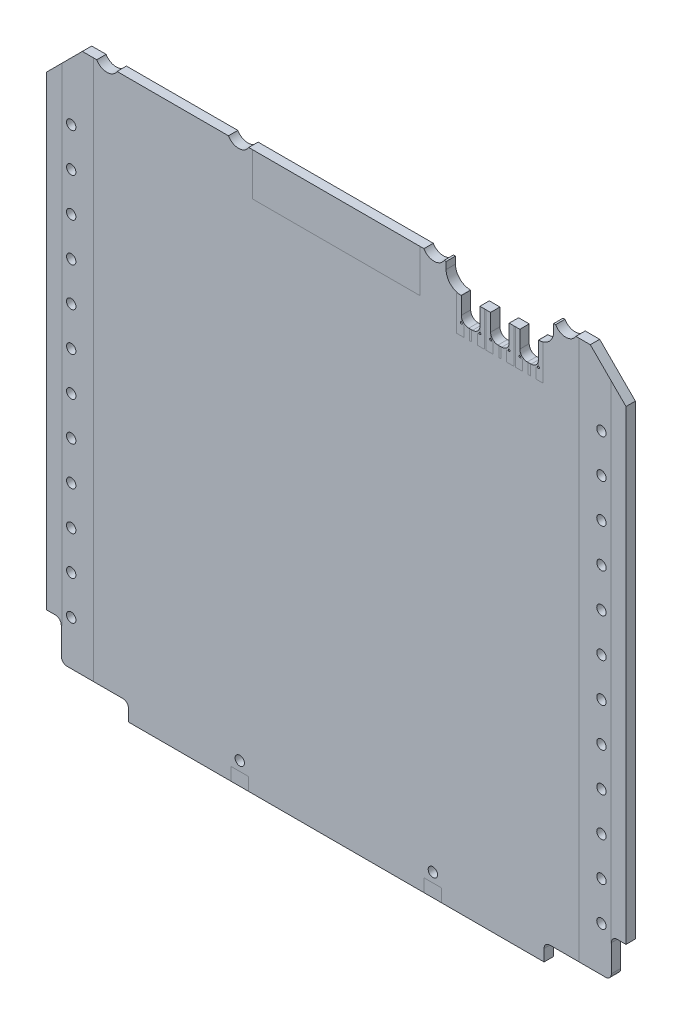
SolidWorks part; units mm, degrees
material "FR4_stuffedProtoboard"
ref_plane "Front Plane" through (0, 0, 0) normal (0, 0, 1) x (1, 0, 0)
ref_plane "Top Plane" through (0, 0, 0) normal (0, 1, 0) x (1, 0, 0)
ref_plane "Right Plane" through (0, 0, 0) normal (1, 0, 0) x (0, 0, -1)
ref_plane "Plane4" through (0, 0, -0.0125) normal (0, 0, -1) x (-1, 0, 0)
sketch "Sketch1" plane through (0, 0, -0.0125) normal (0, 0, -1) x (-1, 0, 0)
  line L4 (49.5, -50) -> (49.5, 45.3)
  line L6 (49.5, 45.3) -> (-49.5, 45.3)
  line L12 (-49.5, 45.3) -> (-49.5, -50)
  line L17 (-49.5, -50) -> (49.5, -50)
  line L18 (0, -50) -> (0, 45.3) construction
  dimension "D7" = 95.3
  dimension "D1" = 99
  dimension "D34" = 50
extrude "basicSize" add sketch "Sketch1" against normal blind 1.6
chamfer "Chamfer1" distance 6.1 angle 45 2 edges at (49.5, 45.3, 0.7875) (-49.5, 45.3, 0.7875)
sketch "Sketch4" plane through (0, 0, 1.5875) normal (0, 0, 1) x (1, 0, 0)
  line L1 (37.4679, 45.3) -> (40.9321, 45.3)
  line L7 (-43.4, 45.3) -> (43.4, 45.3) construction
  line L8 (49.5, 39.2) -> (49.5, -50) construction
  arc A0 (40.9321, 45.3) -> (37.4679, 45.3) centre (39.2, 46.3) cw
  point P5 (39.2, 44.3)
  dimension "D1" = 2
  dimension "D3" = 10.3
  dimension "D2" = 1
extrude "backplaneSideScrewCutout" cut sketch "Sketch4" against normal through all both and the other way through all
pattern_linear "LPattern3" count 2 spacing 22.5 along (-1, 0, 0) of "backplaneSideScrewCutout"
mirror "Mirror3" about plane through (0, 0, 0) normal (1, 0, 0) of "LPattern3"
sketch "Sketch6" plane through (0, 0, 1.5875) normal (0, 0, 1) x (1, 0, 0)
  line L0 (-49.5, -50) -> (-49.5, 39.2) construction
  line L1 (-49.5, -40.4) -> (-47, -40.4)
  line L2 (-49.5, -40.4) -> (-49.5, -50)
  line L4 (-47, -40.4) -> (-47, -47)
  line L5 (49.5, -50) -> (-49.5, -50) construction
  line L6 (-35.5, -50) -> (-49.5, -50)
  line L7 (-35.5, -50) -> (-35.5, -47)
  line L8 (-35.5, -47) -> (-47, -47)
  dimension "D1" = 2.5
  dimension "D2" = 3
  dimension "D3" = 9.6
  dimension "D4" = 14
extrude "Cut-Extrude4" cut sketch "Sketch6" against normal through all
fillet "Fillet1" radius 1 3 edges at (-35.5, -47, 0.7875) (-47, -47, 0.7875) (-47, -40.4, 0.7875)
mirror "Mirror1" about plane through (0, 0, 0) normal (1, 0, 0) of "Cut-Extrude4", "Fillet1"
sketch "Sketch7" plane through (0, 0, 1.5875) normal (0, 0, 1) x (1, 0, 0)
  line L0 (-14.2875, 45.5) -> (-14.2875, 39.912) construction
  line L1 (-14.2875, 45.3) -> (-14.2875, 38.007)
  line L2 (-12.2428, 38.007) -> (-11.8872, 38.007) construction
  line L3 (-14.2875, 38.007) -> (14.2875, 38.007)
  line L4 (14.2875, 45.5) -> (14.2875, 39.912) construction
  line L5 (14.2875, 45.3) -> (14.2875, 38.007)
  line L7 (-14.9679, 45.3) -> (14.9679, 45.3) construction
  line L8 (-14.2875, 45.3) -> (14.2875, 45.3)
extrude "TigerEyeFootprint" cut sketch "Sketch7" against normal blind 0.0001
sketch "thermalContacts_upper" plane through (0, 0, 1.5875) normal (0, 0, 1) x (1, 0, 0)
  line L0 (-49.5, -40.4) -> (-49.5, 39.2) construction
  line L1 (35.5, -50) -> (-35.5, -50) construction
  line L3 (-46.9, 45.3) -> (-46.9, -41.5)
  line L4 (-37.4679, 45.3) -> (-18.4321, 45.3) construction
  line L23 (-46.9, 45.3) -> (-56.3922, 45.3)
  line L24 (-56.3922, 45.3) -> (-56.3922, -41.5)
  line L25 (-56.3922, -41.5) -> (-46.9, -41.5)
  dimension "D1" = 2.6
  dimension "D2" = 8.5
extrude "keepOut_bottom" cut sketch "thermalContacts_upper" against normal blind 0.0001
sketch "Sketch3" plane through (0, 0, 1.5875) normal (0, 0, 1) x (1, 0, 0)
  line L1 (-47, -46) -> (-47, -41.5) construction
  line L2 (-36.5, -47) -> (-46, -47) construction
  line L3 (-14.9679, 45.3) -> (14.9679, 45.3) construction
  line L5 (-49.5, -40.4) -> (-49.5, 39.2) construction
  line L6 (-46.9, -41.5) -> (-46.9, 41.8) construction
  line L7 (-46.9, -41.5) -> (-47, -41.5)
  line L8 (-47, -46) -> (-47, -41.5) construction
  line L9 (-47, -41.5) -> (-46.9, -41.5) construction
  line L10 (0, -50) -> (0, 45.3) construction
  line L11 (35.5, -50) -> (-35.5, -50) construction
  line L12 (-43.4, 45.3) -> (-40.9321, 45.3) construction
  line L13 (-41.5, 45.3) -> (-46.9, 45.3)
  line L14 (-46, -47) -> (-41.5, -47)
  line L15 (-47, -41.5) -> (-47, -46)
  line L16 (-46.9, 45.3) -> (-46.9, -41.5)
  line L17 (-41.5, -47) -> (-41.5, 45.3)
  arc A3 (-47, -46) -> (-46, -47) centre (-46, -46) ccw construction
  arc A4 (-46, -47) -> (-47, -46) centre (-46, -46) cw
  dimension "D1" = 8
extrude "caution_top" cut sketch "Sketch3" against normal blind 0.0001
sketch "hold-downLocations" plane through (0, 0, 1.5875) normal (0, 0, 1) x (1, 0, 0)
  line L1 (-18, -47.8) -> (-15, -47.8) construction
  line L3 (15, -47.8) -> (18, -47.8)
  line L4 (18, -47.8) -> (18, -50)
  line L5 (35.5, -50) -> (-35.5, -50) construction
  line L6 (18, -50) -> (15, -50)
  line L7 (15, -50) -> (15, -47.8)
  line L8 (-15, -47.8) -> (-15, -50) construction
  line L9 (-15, -50) -> (-18, -50) construction
  line L10 (-18, -50) -> (-18, -47.8) construction
  line L11 (0, -50) -> (0, -47.8) construction
  line L12 (-15, -47.8) -> (15, -47.8) construction
  dimension "D1" = 3
  dimension "D2" = 2.2
  dimension "D3" = 3
  dimension "D5" = 30
extrude "hold-downFootprints" cut sketch "hold-downLocations" against normal blind 0.0001
ref_plane "midplane_Z" through (0, 0, 0.7875) normal (0, 0, 1) x (1, 0, 0)
mirror "clearances_top-bottom" about plane through (0, 0, 0.7875) normal (0, 0, 1) of "hold-downFootprints", "caution_top", "keepOut_bottom"
mirror "clearances_side-side" about plane through (0, 0, 0) normal (1, 0, 0) of "clearances_top-bottom"
sketch "Sketch10" plane through (0, 0, -0.0125) normal (0, 0, -1) x (-1, 0, 0)
  line L0 (-15, -47.8) -> (-15, -50) construction
  line L1 (-18, -47.8) -> (-15, -47.8)
  line L2 (-18, -47.8) -> (-18, -44.5)
  line L3 (-18, -44.5) -> (-15, -44.5)
  line L4 (-15, -47.8) -> (-15, -44.5)
  line L5 (-15, -50) -> (15, -50) construction
  line L6 (0, -50) -> (0, -41.5199) construction
  line L7 (15, -47.8) -> (15, -44.5)
  line L8 (18, -44.5) -> (15, -44.5)
  line L9 (18, -47.8) -> (18, -44.5)
  line L10 (18, -47.8) -> (15, -47.8)
  dimension "D1" = 5.5
extrude "bottomsideShelfKeepouts" cut sketch "Sketch10" against normal up to surface (0.0001 mm away) up to face at (16.5, -48.9, -0.0124)
sketch "recommendedBuildArea" [suppressed] plane through (0, 0, 1.5875) normal (0, 0, 1) x (1, 0, 0)
  line L0 (51.1146, 38.007) -> (51.1146, 56.8216) construction
  line L1 (-35.5, -45.5) -> (-46.8, -45.5) construction
  line L2 (-35.5, -47) -> (-35.5, -45.5) construction
  line L3 (35.5, -47) -> (35.5, -45.5) construction
  line L4 (14.2875, 45.3) -> (-14.2875, 45.3)
  line L5 (-14.2875, 45.3) -> (-14.2875, 38.007)
  line L6 (-14.2875, 38.007) -> (14.2875, 38.007)
  line L7 (-46.8, 41.9) -> (-49.5, 39.2)
  line L8 (-49.5, 39.2) -> (-49.5, -40.4)
  line L9 (-49.5, -40.4) -> (-48, -40.4)
  line L10 (-46.8, -41.5) -> (-46.8, 41.9)
  line L11 (-47, -41.4) -> (-47, -41.5)
  line L12 (-47, -41.4) -> (-47, -41.5)
  line L13 (-47, -41.5) -> (-46.8, -41.5)
  line L14 (35.5, -45.5) -> (46.8, -45.5) construction
  line L15 (54.1146, 35.007) -> (54.1146, 77.997)
  line L16 (54.1146, 77.997) -> (43.8, 42.325)
  line L17 (-46.8, -45.5) -> (-46.8, 41.9) construction
  line L20 (43.8, 42.325) -> (43.8, -42.5)
  line L21 (14.2875, 38.007) -> (14.2875, 45.3)
  line L22 (32.5, -42.5) -> (43.8, -42.5)
  line L23 (-14.2875, 45.3) -> (-14.2875, 38.007)
  line L24 (-14.2875, 38.007) -> (51.1146, 38.007)
  line L25 (32.5, -47) -> (32.5, -42.5)
  line L26 (32.5, -47) -> (32.5, -47)
  line L27 (21, -47) -> (32.5, -47)
  line L28 (21, -45) -> (21, -47)
  line L29 (46.8, -41.5) -> (47, -41.5)
  line L30 (46.8, -41.5) -> (47, -41.5)
  line L31 (46.8, 41.9) -> (46.8, -41.5)
  line L32 (48, -40.4) -> (49.5, -40.4)
  line L33 (49.5, -40.4) -> (49.5, 39.2)
  line L34 (49.5, 39.2) -> (46.8, 41.9)
  line L35 (47, -41.5) -> (47, -41.4)
  line L36 (12, -45) -> (21, -45)
  line L37 (47, -41.5) -> (47, -41.4)
  line L38 (46.8, 41.9) -> (46.8, -45.5) construction
  line L39 (12, -47) -> (12, -45)
  line L40 (-12, -47) -> (12, -47)
  line L41 (-12, -45) -> (-12, -47)
  line L42 (-21, -45) -> (-12, -45)
  line L43 (-21, -47) -> (-21, -45)
  line L44 (-32.5, -47) -> (-21, -47)
  line L45 (-32.5, -47) -> (-32.5, -47)
  line L46 (-32.5, -47) -> (-32.5, -42.5)
  line L47 (-32.5, -42.5) -> (-43.8, -42.5)
  line L48 (-43.8, -42.5) -> (-43.8, 34.7661)
  line L49 (-43.8, 34.7661) -> (-43.8, 34.7661)
  line L50 (-43.8, 34.7661) -> (-39.8793, 42.3)
  line L51 (-17.2875, 42.3) -> (-39.8793, 42.3)
  line L52 (-17.2875, 42.3) -> (-17.2875, 35.007)
  line L53 (-17.2875, 35.007) -> (54.1146, 35.007)
  line L59 (-47, -41.5) -> (-46.8, -41.5)
  line L72 (-15, -48) -> (-15, -50)
  line L73 (-15, -50) -> (15, -50)
  line L74 (15, -50) -> (15, -48)
  line L75 (15, -48) -> (18, -48)
  line L76 (18, -48) -> (18, -50)
  line L77 (18, -50) -> (35.5, -50)
  line L78 (35.5, -50) -> (35.5, -48)
  line L79 (36.5, -47) -> (41.5, -47)
  line L80 (41.5, -47) -> (41.5, 45.3)
  line L81 (41.5, 45.3) -> (40.9321, 45.3)
  line L82 (37.4679, 45.3) -> (34.25, 45.3)
  line L83 (34.25, 45.3) -> (34.25, 38.35)
  line L84 (34.25, 38.35) -> (30.75, 38.35)
  line L85 (30.75, 38.35) -> (30.75, 45.3)
  line L86 (30.75, 45.3) -> (29.25, 45.3)
  line L87 (29.25, 45.3) -> (29.25, 38.35)
  line L88 (29.25, 38.35) -> (25.75, 38.35)
  line L89 (25.75, 38.35) -> (25.75, 45.3)
  line L90 (25.75, 45.3) -> (24.25, 45.3)
  line L91 (24.25, 45.3) -> (24.25, 38.35)
  line L92 (24.25, 38.35) -> (20.75, 38.35)
  line L93 (20.75, 38.35) -> (20.75, 45.3)
  line L94 (20.75, 45.3) -> (18.4321, 45.3)
  line L95 (14.9679, 45.3) -> (14.2875, 45.3)
  line L96 (14.2875, 45.3) -> (14.2875, 38.007)
  line L97 (14.2875, 38.007) -> (-14.2875, 38.007)
  line L98 (-14.2875, 38.007) -> (-14.2875, 45.3)
  line L99 (-14.2875, 45.3) -> (-14.9679, 45.3)
  line L100 (-18.4321, 45.3) -> (-37.4679, 45.3)
  line L101 (-40.9321, 45.3) -> (-41.5, 45.3)
  line L102 (41.5, -47) -> (41.5, 45.3)
  line L103 (-41.5, -47) -> (-36.5, -47)
  line L104 (-35.5, -48) -> (-35.5, -50)
  line L105 (-35.5, -50) -> (-18, -50)
  line L106 (-18, -50) -> (-18, -48)
  line L107 (-18, -48) -> (-15, -48)
  line L108 (-15, -48) -> (-15, -50) construction
  line L109 (-15, -50) -> (15, -50) construction
  line L110 (15, -50) -> (15, -48) construction
  line L111 (15, -48) -> (18, -48) construction
  line L112 (18, -48) -> (18, -50) construction
  line L113 (18, -50) -> (35.5, -50) construction
  line L114 (35.5, -50) -> (35.5, -47) construction
  line L115 (35.5, -47) -> (41.5, -47) construction
  line L133 (51.1146, 38.007) -> (-14.2875, 38.007)
  line L134 (-14.2875, 38.007) -> (-14.2875, 45.3)
  line L136 (-14.2875, 45.3) -> (-41.7, 45.3) construction
  line L139 (-41.5, -47) -> (-35.5, -47) construction
  line L140 (-35.5, -47) -> (-35.5, -50) construction
  line L141 (-35.5, -50) -> (-18, -50) construction
  line L142 (-18, -50) -> (-18, -48) construction
  line L143 (-18, -48) -> (-15, -48) construction
  line L144 (-46.8, 35.5) -> (-41.7, 45.3) construction
  line L160 (-41.5, 45.3) -> (-41.5, -47)
  line L161 (-41.5, 45.3) -> (-41.5, -47)
  line L162 (-46.8, 41.9) -> (-46.8, 35.5) construction
  line L163 (51.1146, 56.8216) -> (46.8, 41.9) construction
  arc A1 (-47, -41.4) -> (-48, -40.4) centre (-48, -41.4) ccw
  arc A3 (48, -40.4) -> (47, -41.4) centre (48, -41.4) ccw
  arc A10 (36.5, -47) -> (35.5, -48) centre (36.5, -48) ccw
  arc A11 (37.4679, 45.3) -> (40.9321, 45.3) centre (39.2, 46.3) ccw
  arc A12 (14.9679, 45.3) -> (18.4321, 45.3) centre (16.7, 46.3) ccw
  arc A13 (-18.4321, 45.3) -> (-14.9679, 45.3) centre (-16.7, 46.3) ccw
  arc A14 (-40.9321, 45.3) -> (-37.4679, 45.3) centre (-39.2, 46.3) ccw
  arc A15 (-35.5, -48) -> (-36.5, -47) centre (-36.5, -48) ccw
  dimension "D5" = 1.5
  dimension "D1" = 0
  dimension "D2" = 0
  dimension "D3" = 0
  dimension "D4" = 0
  dimension "D6" = 3
ref_point "rail midpoint"
sketch "locatorSketch" plane through (0, 0, 1.5875) normal (0, 0, 1) x (1, 0, 0)
  line L0 (-12.2428, 39.531) -> (12.2428, 38.007) construction
  line L1 (12.2428, 39.531) -> (-12.2428, 38.007) construction
  line L2 (-21.9628, 39.277) -> (-33.0372, 38.261) construction
  line L3 (-33.0372, 39.277) -> (-21.9628, 38.261) construction
  line L4 (-12.2428, 38.261) -> (-12.2428, 38.007)
  line L5 (-11.8872, 38.261) -> (-12.2428, 38.261)
  line L6 (-11.8872, 38.007) -> (-11.8872, 38.261)
  line L7 (-12.2428, 38.007) -> (-11.8872, 38.007)
  line L8 (-12.2428, 38.261) -> (-12.2428, 38.007)
  line L9 (-11.8872, 38.261) -> (-12.2428, 38.261)
  line L10 (-11.8872, 38.007) -> (-11.8872, 38.261)
  line L11 (-12.2428, 38.007) -> (-11.8872, 38.007)
  line L12 (-12.2428, 39.531) -> (-12.2428, 39.277)
  line L13 (-11.8872, 39.531) -> (-12.2428, 39.531)
  line L14 (-11.8872, 39.277) -> (-11.8872, 39.531)
  line L15 (-12.2428, 39.277) -> (-11.8872, 39.277)
  line L16 (-12.2428, 39.531) -> (-12.2428, 39.277)
  line L17 (-11.8872, 39.531) -> (-12.2428, 39.531)
  line L18 (-11.8872, 39.277) -> (-11.8872, 39.531)
  line L19 (-12.2428, 39.277) -> (-11.8872, 39.277)
  line L20 (11.8872, 39.531) -> (11.8872, 39.277)
  line L21 (12.2428, 39.531) -> (11.8872, 39.531)
  line L22 (12.2428, 39.277) -> (12.2428, 39.531)
  line L23 (11.8872, 39.277) -> (12.2428, 39.277)
  line L24 (11.8872, 39.531) -> (11.8872, 39.277)
  line L25 (12.2428, 39.531) -> (11.8872, 39.531)
  line L26 (12.2428, 39.277) -> (12.2428, 39.531)
  line L27 (11.8872, 39.277) -> (12.2428, 39.277)
  line L28 (11.8872, 38.261) -> (11.8872, 38.007)
  line L29 (12.2428, 38.261) -> (11.8872, 38.261)
  line L30 (12.2428, 38.007) -> (12.2428, 38.261)
  line L31 (11.8872, 38.007) -> (12.2428, 38.007)
  line L32 (11.8872, 38.261) -> (11.8872, 38.007)
  line L33 (12.2428, 38.261) -> (11.8872, 38.261)
  line L34 (12.2428, 38.007) -> (12.2428, 38.261)
  line L35 (11.8872, 38.007) -> (12.2428, 38.007)
  line L38 (-21.9628, 39.531) -> (-21.9628, 39.277)
  line L39 (-21.6072, 39.531) -> (-21.9628, 39.531)
  line L40 (-21.6072, 39.277) -> (-21.6072, 39.531)
  line L41 (-21.9628, 39.277) -> (-21.6072, 39.277)
  line L42 (-21.9628, 39.531) -> (-21.9628, 39.277)
  line L43 (-21.6072, 39.531) -> (-21.9628, 39.531)
  line L44 (-21.6072, 39.277) -> (-21.6072, 39.531)
  line L45 (-21.9628, 39.277) -> (-21.6072, 39.277)
  line L46 (-33.3928, 38.261) -> (-33.3928, 38.007)
  line L47 (-33.0372, 38.261) -> (-33.3928, 38.261)
  line L48 (-33.0372, 38.007) -> (-33.0372, 38.261)
  line L49 (-33.3928, 38.007) -> (-33.0372, 38.007)
  line L50 (-33.3928, 38.261) -> (-33.3928, 38.007)
  line L51 (-33.0372, 38.261) -> (-33.3928, 38.261)
  line L52 (-33.0372, 38.007) -> (-33.0372, 38.261)
  line L53 (-33.3928, 38.007) -> (-33.0372, 38.007)
  line L55 (-21.9628, 38.261) -> (-21.9628, 38.007)
  line L56 (-21.6072, 38.261) -> (-21.9628, 38.261)
  line L57 (-21.6072, 38.007) -> (-21.6072, 38.261)
  line L58 (-21.9628, 38.007) -> (-21.6072, 38.007)
  line L59 (-21.9628, 38.261) -> (-21.9628, 38.007)
  line L60 (-21.6072, 38.261) -> (-21.9628, 38.261)
  line L61 (-21.6072, 38.007) -> (-21.6072, 38.261)
  line L62 (-21.9628, 38.007) -> (-21.6072, 38.007)
  line L63 (-33.3928, 39.531) -> (-33.3928, 39.277)
  line L64 (-33.0372, 39.531) -> (-33.3928, 39.531)
  line L65 (-33.0372, 39.277) -> (-33.0372, 39.531)
  line L66 (-33.3928, 39.277) -> (-33.0372, 39.277)
  line L67 (-33.3928, 39.531) -> (-33.3928, 39.277)
  line L68 (-33.0372, 39.531) -> (-33.3928, 39.531)
  line L69 (-33.0372, 39.277) -> (-33.0372, 39.531)
  line L70 (-33.3928, 39.277) -> (-33.0372, 39.277)
  dimension "D1" = 0
  dimension "D2" = 0
  dimension "D3" = 0
  dimension "D4" = 0
  dimension "D5" = 0
  dimension "D6" = 0
  dimension "D7" = 0
  dimension "D8" = 0
sketch "Sketch8" plane through (0, 0, 1.5875) normal (0, 0, 1) x (1, 0, 0)
  line L0 (-49.5, -40.4) -> (-48, -40.4) construction
  line L2 (-49.5, -40.4) -> (-49.5, 39.2) construction
  line L3 (-41.5, 45.3) -> (-43.4, 45.3) construction
  line L4 (-18, -47.8) -> (-15, -47.8) construction
  line L5 (-45.3, 33.5) -> (-46.9, 33.5) construction
  line L6 (-46.9, 41.8) -> (-46.9, -41.5) construction
  line L7 (-16.5, -46.2) -> (-16.5, -47.8) construction
  line L8 (-18, -47.8) -> (-15, -47.8) construction
  circle A0 centre (-45.3, 33.5) radius 0.8
  circle A1 centre (-45.3, 26.8727) radius 0.8
  circle A2 centre (-45.3, 20.2455) radius 0.8
  circle A3 centre (-45.3, 13.6182) radius 0.8
  circle A4 centre (-45.3, 6.9909) radius 0.8
  circle A5 centre (-45.3, 0.3636) radius 0.8
  circle A6 centre (-45.3, -6.2636) radius 0.8
  circle A7 centre (-45.3, -12.8909) radius 0.8
  circle A8 centre (-45.3, -19.5182) radius 0.8
  circle A9 centre (-45.3, -26.1455) radius 0.8
  circle A10 centre (-45.3, -32.7727) radius 0.8
  circle A11 centre (-45.3, -39.4) radius 0.8
  circle A12 centre (-16.5, -46.2) radius 0.8
  point P35 (-16.5, -47.8)
  dimension "D1" = 1.6
  dimension "D3" = 1
  dimension "D5" = 4.2
  dimension "D6" = 11.8
  dimension "D2" = 12
extrude "springPinHoleSeed" cut sketch "Sketch8" against normal blind 10
mirror "Mirror4" about plane through (0, 0, 0) normal (1, 0, 0) of "springPinHoleSeed"
sketch "Sketch9" plane through (0, 0, 1.5875) normal (0, 0, 1) x (1, 0, 0)
  circle A0 centre (-45.3, 33.5) radius 1.35
  dimension "D1" = 2.7
sketch "bottomsideKeepout_trace" plane through (0, 0, -0.0125) normal (0, 0, -1) x (-1, 0, 0)
  line L0 (18, -50) -> (18, -44.5) construction
  line L1 (18, -44.5) -> (15, -44.5) construction
  line L2 (15, -44.5) -> (15, -50) construction
  line L3 (-15, -44.5) -> (-15, -50) construction
  line L4 (-15, -44.5) -> (-18, -44.5) construction
  line L5 (-18, -50) -> (-18, -44.5) construction
  line L6 (18, -50) -> (18, -44.5)
  line L7 (18, -44.5) -> (15, -44.5)
  line L8 (15, -44.5) -> (15, -50)
  line L9 (-15, -44.5) -> (-15, -50)
  line L10 (-15, -44.5) -> (-18, -44.5)
  line L11 (-18, -50) -> (-18, -44.5)
  line L12 (15, -50) -> (18, -50) construction
  line L13 (-15, -50) -> (-18, -50) construction
  line L14 (15, -50) -> (18, -50)
  line L15 (-15, -50) -> (-18, -50)
sketch "Sketch11" plane through (0, 0, 1.5875) normal (0, 0, 1) x (1, 0, 0)
  line L6 (34.54, 41.56) -> (31.36, 41.56)
  line L8 (34.54, 41.56) -> (34.54, 37.36)
  line L11 (34.54, 37.36) -> (31.36, 37.36)
  line L12 (31.36, 41.56) -> (31.36, 37.36)
  line L13 (34.54, 41.56) -> (31.36, 37.36) construction
  line L14 (34.54, 37.36) -> (31.36, 41.56) construction
  line L18 (29.54, 41.56) -> (26.36, 41.56)
  line L19 (29.54, 41.56) -> (29.54, 37.36)
  line L20 (29.54, 37.36) -> (26.36, 37.36)
  line L21 (26.36, 41.56) -> (26.36, 37.36)
  line L22 (29.54, 41.56) -> (26.36, 37.36) construction
  line L23 (29.54, 37.36) -> (26.36, 41.56) construction
  line L24 (24.54, 41.56) -> (21.36, 41.56)
  line L25 (24.54, 41.56) -> (24.54, 37.36)
  line L26 (24.54, 37.36) -> (21.36, 37.36)
  line L27 (21.36, 41.56) -> (21.36, 37.36)
  line L28 (24.54, 41.56) -> (21.36, 37.36) construction
  line L29 (24.54, 37.36) -> (21.36, 41.56) construction
  line L30 (18.4321, 45.3) -> (37.4679, 45.3) construction
  line L31 (16.7, 46.3) -> (39.2, 46.3) construction
  point P4 (32.95, 39.46)
  point P10 (27.95, 46.3)
  point P15 (27.95, 39.46)
  point P20 (22.95, 39.46)
  dimension "D5" = 5
  dimension "D1" = 3.18
  dimension "D2" = 4.2
  dimension "D4" = 3
  dimension "D6" = 3.74
extrude "Cut-Extrude5" cut sketch "Sketch11" against normal blind 10
fillet "Fillet2" radius 1.27 6 edges at (24.54, 37.36, 0.7875) (29.54, 37.36, 0.7875) (34.54, 37.36, 0.7875) (31.36, 37.36, 0.7875) (26.36, 37.36, 0.7875) (21.36, 37.36, 0.7875)
hole_wizard "Ø0.32 (0.32) Diameter Hole1" positions "Sketch12" profile "Sketch13" hole size "Ø0.32" standard "ANSI Metric"
sketch "Sketch12" plane through (0, 0, 1.5875) normal (0, 0, 1) x (1, 0, 0)
  line L1 (34.54, 38.63) -> (34.54, 41.56) construction
  line L2 (31.36, 41.56) -> (31.36, 38.63) construction
  line L3 (32.95, 37.36) -> (34.7997, 37.36) construction
  line L4 (32.63, 37.36) -> (33.27, 37.36) construction
  point P0 (34.54, 37.52)
  point P2 (31.36, 37.52)
  point P16 (29.54, 37.52)
  point P17 (26.36, 37.52)
  point P18 (24.54, 37.52)
  point P19 (21.36, 37.52)
  dimension "D2" = 5
  dimension "D3" = 0.16
  dimension "D1" = 3
sketch "Sketch13" plane through (34.54, 37.52, 1.5875) normal (1, 0, 0) x (0, -1, 0)
  line L0 (0, 0) -> (0, 9.6211)
  line L1 (0, 9.6211) -> (0.16, 9.525)
  line L2 (0.16, 9.525) -> (0.16, 0)
  line L5 (0.16, 0) -> (0, 0)
  line L10 (0, 9.6211) -> (-0.16, 9.525) construction
  line L11 (0, -6.35) -> (0, 107.95) construction
  dimension "Hole Dia." = 0.32
  dimension "Hole Depth" = 9.525
  dimension "Drill Angle" = 118
sketch "Sketch14" plane through (0, 0, 1.5875) normal (0, 0, 1) x (1, 0, 0)
  line L1 (35.325, 41.56) -> (34.54, 41.56)
  line L2 (35.325, 41.56) -> (35.325, 35.57)
  line L3 (35.325, 35.57) -> (34.095, 35.57)
  line L4 (30.575, 41.56) -> (30.575, 35.57)
  line L5 (35.325, 41.56) -> (30.575, 35.57) construction
  line L6 (35.325, 35.57) -> (30.575, 41.56) construction
  line L7 (32.95, 37.36) -> (32.95, 35.57) construction
  line L8 (32.63, 37.36) -> (33.27, 37.36) construction
  line L9 (31.805, 35.57) -> (31.805, 37.36)
  line L10 (32.76, 37.36) -> (33.14, 37.36)
  line L11 (32.76, 37.36) -> (32.76, 35.57)
  line L12 (32.76, 35.57) -> (33.14, 35.57)
  line L13 (33.14, 37.36) -> (33.14, 35.57)
  line L14 (32.76, 37.36) -> (33.14, 35.57) construction
  line L15 (32.76, 35.57) -> (33.14, 37.36) construction
  line L16 (34.095, 35.57) -> (34.095, 37.36)
  line L17 (33.14, 35.57) -> (32.76, 35.57)
  line L18 (31.36, 41.56) -> (31.36, 38.63) construction
  line L19 (34.54, 38.63) -> (34.54, 41.56) construction
  line L20 (31.36, 41.56) -> (31.36, 38.63)
  line L21 (34.54, 38.63) -> (34.54, 41.56)
  line L22 (32.76, 37.36) -> (33.14, 37.36)
  line L23 (31.36, 41.56) -> (30.575, 41.56)
  line L24 (31.805, 37.36) -> (31.36, 37.36)
  line L25 (34.095, 37.36) -> (34.54, 37.36)
  line L26 (31.36, 37.68) -> (31.36, 38.63)
  line L27 (34.54, 37.68) -> (34.54, 38.63)
  line L28 (31.805, 35.57) -> (30.575, 35.57)
  circle A2 centre (31.36, 37.52) radius 0.16 construction
  circle A3 centre (34.54, 37.52) radius 0.16 construction
  arc A6 (31.36, 37.68) -> (31.36, 37.36) centre (31.36, 37.52) ccw
  arc A7 (34.54, 37.36) -> (34.54, 37.68) centre (34.54, 37.52) ccw
  point P4 (32.95, 38.565)
  point P15 (32.95, 36.465)
  dimension "D1" = 5.99
  dimension "D2" = 4.75
  dimension "D3" = 2.29
  dimension "D4" = 0.38
extrude "Boss-Extrude1" add sketch "Sketch14" along normal blind 0.0001 contours A6 L26 L20 L23 L4 L28 L9 L24 | L13 L10 L11 L12 | A7 L25 L16 L3 L2 L1 L21 L27 region at (34.8451, 38.2662, 1.5875) region at (31.0549, 38.2662, 1.5875) region at (32.95, 36.465, 1.5875)
pattern_linear "LPattern4" count 3 spacing 5 along (-1, 0, 0) of "Boss-Extrude1"
sketch "Sketch15" plane through (0, 0, 1.5875) normal (0, 0, 1) x (1, 0, 0)
  line L0 (18.4321, 45.3) -> (37.4679, 45.3) construction
  line L1 (18.76, 45.3) -> (37.14, 45.3)
  line L2 (18.76, 45.3) -> (18.76, 44.1)
  line L3 (21.3, 41.56) -> (34.6, 41.56)
  line L4 (37.14, 45.3) -> (37.14, 44.1)
  line L5 (18.76, 45.3) -> (37.14, 41.56) construction
  line L6 (18.76, 41.56) -> (37.14, 45.3) construction
  line L7 (34.54, 41.56) -> (31.36, 41.56) construction
  line L9 (21.36, 37.68) -> (21.36, 41.56) construction
  line L11 (34.54, 37.68) -> (34.54, 41.56) construction
  arc A0 (34.6, 41.56) -> (37.14, 44.1) centre (34.6, 44.1) ccw
  arc A1 (18.76, 44.1) -> (21.3, 41.56) centre (21.3, 44.1) ccw
  point P4 (27.95, 43.43)
  dimension "D3" = 2.54
  dimension "D1" = 2.6
  dimension "D2" = 2.6
extrude "Cut-Extrude6" cut sketch "Sketch15" against normal through all and the other way through all
